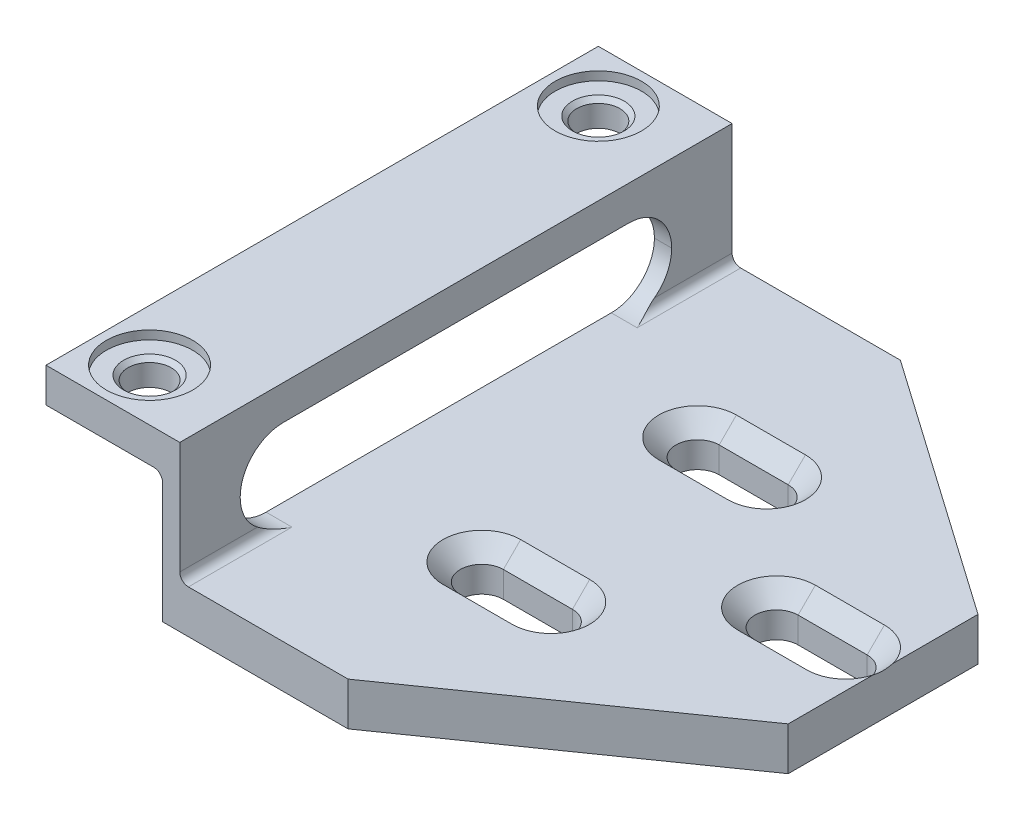
SolidWorks part; units mm, degrees
ref_plane "Front Plane" through (0, 0, 0) normal (0, 0, 1) x (1, 0, 0)
ref_plane "Top Plane" through (0, 0, 0) normal (0, 1, 0) x (1, 0, 0)
ref_plane "Right Plane" through (0, 0, 0) normal (1, 0, 0) x (0, 0, -1)
sketch "Sketch1" plane through (0, 0, 0) normal (0, 1, 0) x (1, 0, 0)
  line L0 (0, 40.64) -> (38.1, 13.9621)
  line L1 (-44.45, -40.64) -> (0, -40.64)
  line L2 (-44.45, -40.64) -> (-44.45, 40.64)
  line L3 (-44.45, 40.64) -> (0, 40.64)
  line L4 (38.1, -13.9621) -> (38.1, 13.9621)
  line L5 (-5.08, 19.05) -> (5.08, 19.05)
  line L6 (-5.08, 12.7) -> (5.08, 12.7)
  line L7 (0, -40.64) -> (38.1, -13.9621)
  line L8 (-5.08, -12.7) -> (5.08, -12.7)
  line L9 (-5.08, -19.05) -> (5.08, -19.05)
  line L10 (22.4163, 3.175) -> (32.5763, 3.175)
  line L11 (22.4163, -3.175) -> (32.5763, -3.175)
  circle A0 centre (-36.83, 33.02) radius 3.175
  circle A1 centre (-36.83, -33.02) radius 3.175
  arc A5 (5.08, 12.7) -> (5.08, 19.05) centre (5.08, 15.875) ccw
  arc A6 (-5.08, 19.05) -> (-5.08, 12.7) centre (-5.08, 15.875) ccw
  arc A7 (5.08, -19.05) -> (5.08, -12.7) centre (5.08, -15.875) ccw
  arc A8 (-5.08, -12.7) -> (-5.08, -19.05) centre (-5.08, -15.875) ccw
  arc A9 (22.4163, 3.175) -> (22.4163, -3.175) centre (22.4163, 0) ccw
  arc A10 (32.5763, -3.175) -> (32.5763, 3.175) centre (32.5763, 0) ccw
  point P0 (0, 0)
  point P4 (38.1, 0)
  dimension "D1" = 6.35
  dimension "D2" = 66.04
  dimension "D3" = 7.62
  dimension "D4" = 7.62
  dimension "D5" = 7.62
  dimension "D6" = 38.1
  dimension "D7" = 145
  dimension "D8" = 145
  dimension "D9" = 44.45
extrude "Boss-Extrude1" add sketch "Sketch1" along normal blind 6.35
sketch "Sketch10" plane through (0, 6.35, 0) normal (0, 1, 0) x (1, 0, 0)
  line L1 (-44.45, 40.64) -> (-24.765, 40.64)
  line L2 (-44.45, 40.64) -> (-44.45, -40.64)
  line L3 (-44.45, -40.64) -> (-24.765, -40.64)
  line L4 (-24.765, -40.64) -> (-24.765, 40.64)
  circle A0 centre (-36.83, -33.02) radius 3.175 construction
  circle A1 centre (-36.83, 33.02) radius 3.175 construction
  circle A2 centre (-36.83, -33.02) radius 3.175
  circle A3 centre (-36.83, 33.02) radius 3.175
  dimension "D1" = 19.685
extrude "Boss-Extrude4" add sketch "Sketch10" along normal blind 17.78
sketch "Sketch12" plane through (0, 0, 0) normal (0, -1, 0) x (1, 0, 0)
  line L0 (0, -40.64) -> (-44.45, -40.64) construction
  line L1 (-44.45, 40.64) -> (-27.305, 40.64)
  line L2 (-44.45, 40.64) -> (-44.45, -40.64)
  line L3 (-44.45, -40.64) -> (-27.305, -40.64)
  line L5 (-27.305, 40.64) -> (-27.305, -40.64)
  line L6 (-44.45, 40.64) -> (0, 40.64) construction
  point P9 (-22.225, 40.64)
  dimension "D1" = 5.08
extrude "Cut-Extrude5" cut sketch "Sketch12" against normal blind 12.7
sketch "Sketch14" plane through (0, 24.13, 0) normal (0, 1, 0) x (1, 0, 0)
  circle A0 centre (-36.83, 33.02) radius 6.35
  circle A1 centre (-36.83, -33.02) radius 6.35
  dimension "D1" = 12.7
extrude "Cut-Extrude9" cut sketch "Sketch14" against normal blind 1.27
chamfer "Chamfer2" distance 0.635 angle 45 2 edges at (-36.83, 22.86, -29.845) (-36.83, 22.86, 36.195)
sketch "Sketch15" plane through (-24.765, 0, 0) normal (1, 0, 0) x (0, 0, -1)
  line L0 (-31.75, 6.35) -> (-31.75, 19.05)
  line L1 (-40.64, 6.35) -> (-13.9621, 6.35) construction
  line L2 (-31.75, 19.05) -> (31.75, 19.05)
  line L3 (31.75, 19.05) -> (31.75, 6.35)
  line L4 (13.9621, 6.35) -> (40.64, 6.35) construction
  line L5 (31.75, 6.35) -> (-31.75, 6.35)
  line L6 (-40.64, 24.13) -> (-40.64, 6.35) construction
  line L7 (40.64, 24.13) -> (40.64, 6.35) construction
  line L8 (-40.64, 24.13) -> (40.64, 24.13) construction
  dimension "D1" = 8.89
  dimension "D2" = 8.89
  dimension "D3" = 5.08
extrude "Cut-Extrude10" cut sketch "Sketch15" against normal blind 36.576
sketch "Sketch16" plane through (0, 0, -40.64) normal (0, 0, -1) x (-1, 0, 0)
  line L0 (27.305, 12.7) -> (27.305, 19.05)
  line L1 (27.305, 19.05) -> (44.45, 19.05)
  line L2 (44.45, 24.13) -> (44.45, 12.7) construction
  line L3 (44.45, 19.05) -> (44.45, 12.7)
  line L4 (44.45, 12.7) -> (27.305, 12.7)
  dimension "D1" = 5.08
extrude "Cut-Extrude11" cut sketch "Sketch16" against normal blind 84.836
fillet "Fillet1" radius 1.27 4 edges at (-27.305, 19.05, 36.195) (-27.305, 19.05, -36.195) (-24.765, 6.35, 36.195) (-24.765, 6.35, -36.195)
fillet "Fillet2" radius 6.35 4 edges at (-25.4, 6.35, 31.75) (-25.4, 6.35, -31.75) (-26.67, 19.05, -31.75) (-26.67, 19.05, 31.75)
chamfer "Chamfer3" distance 2.54 angle 45 12 edges at (0, 6.35, 19.05) (8.255, 6.35, 15.875) (-8.255, 6.35, 15.875) (0, 6.35, 12.7) (27.4963, 6.35, 3.175) (35.7513, 6.35, 0) (19.2413, 6.35, 0) (27.4963, 6.35, -3.175) (0, 6.35, -12.7) (8.255, 6.35, -15.875) (-8.255, 6.35, -15.875) (0, 6.35, -19.05)
equation "\"0.05n\"=0.0937008"
